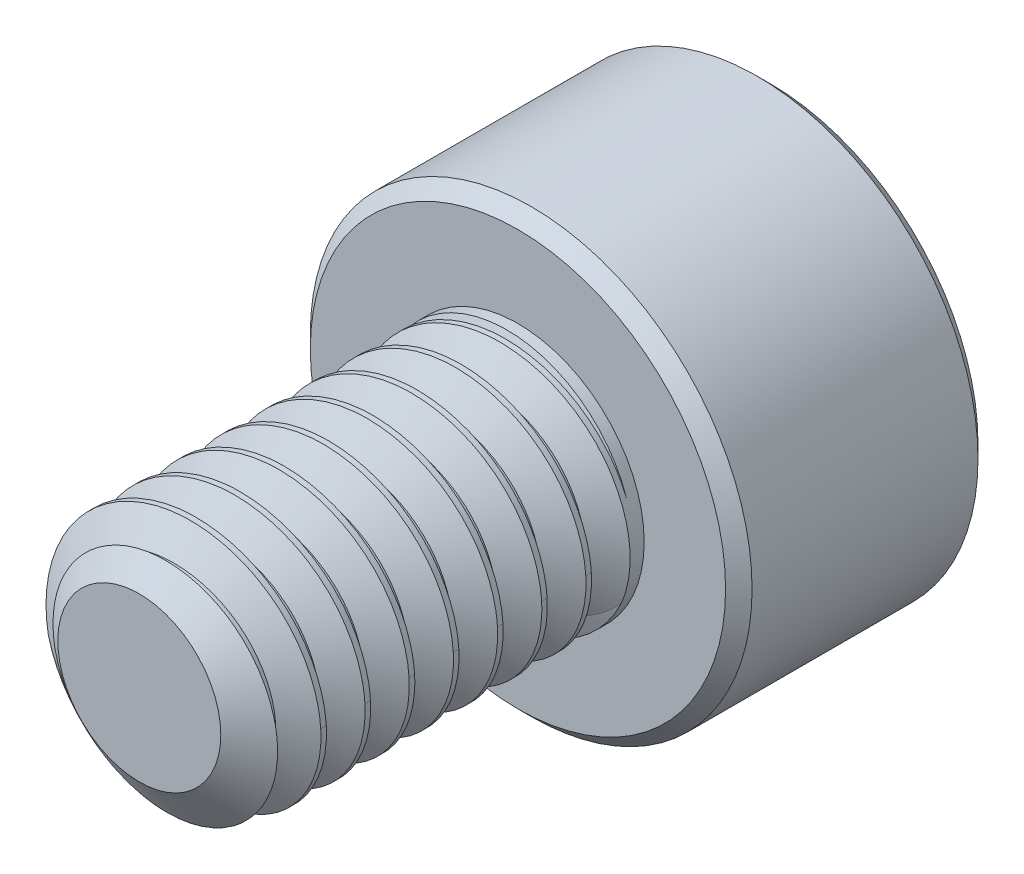
SolidWorks part; units mm, degrees
material "Plain Carbon Steel"
ref_plane "Front Plane" through (0, 0, 0) normal (0, 0, 1) x (1, 0, 0)
ref_plane "Top Plane" through (0, 0, 0) normal (0, 1, 0) x (1, 0, 0)
ref_plane "Right Plane" through (0, 0, 0) normal (1, 0, 0) x (0, 0, -1)
sketch "Sketch1" plane through (0, 0, 0) normal (0, 0, 1) x (1, 0, 0)
  circle A0 centre (0, 0) radius 2
  dimension "OD" = 4
extrude "Extrude1" add sketch "Sketch1" against normal blind 6
sketch "Sketch2" plane through (0, 0, 0) normal (0, 0, 1) x (1, 0, 0)
  circle A0 centre (0, 0) radius 2 construction
  circle A1 centre (0, 0) radius 2
curve "Helix/Spiral1" pitch 0.7 height 6.7 radius 2 centre (0, 0, 0) axis (0, 0, -1) start towards (0, 1, 0) parameters "pitch"=0.7
sketch "Sketch3" plane through (0, 0, 0) normal (1, 0, 0) x (0, 0, -1)
  line L0 (-0.6125, 2) -> (-0.35, 1.5453)
  line L1 (-0.35, 1.5453) -> (-0.2625, 1.5453)
  line L2 (-0.2625, 1.5453) -> (0, 2)
  line L3 (-0.6125, 2) -> (0, 2)
  line L4 (-0.3063, 2) -> (-0.3063, 1.5453) construction
  line L5 (-0.4813, 1.7727) -> (-0.1313, 1.7727) construction
  line L6 (0, 2) -> (0, -2) construction
  line L7 (0, -2) -> (6, -2) construction
  point P11 (3.15, -2)
  dimension "D1" = 0.0875
  dimension "D2" = 0.35
  dimension "D3" = 60
  dimension "D4" = 3.15
sweep "Cut-Sweep1" cut profiles "Sketch3" path "Helix/Spiral1" align with end faces yes
sketch "Sketch4" plane through (0, 0, 0) normal (1, 0, 0) x (0, 0, -1)
  line L0 (0.4962, 2) -> (0, 1.2913)
  line L1 (0, 1.2913) -> (0, 2)
  line L2 (0.4962, 2) -> (0, 2)
  line L3 (-0.6125, 2) -> (0, 2) construction
  line L4 (0, 0) -> (7.0209, 0) construction
  dimension "D1" = 55
  dimension "D2" = 0.254
revolve "Cut-Revolve1" cut sketch "Sketch4" angle 360 about L4
sketch "Sketch5" plane through (0, 0, 0) normal (1, 0, 0) x (0, 0, -1)
  line L0 (6, -1.8828) -> (6, 1.3901) construction
  line L1 (6, 2) -> (0.1203, 2)
  line L2 (6, 2) -> (6, 0)
  line L3 (6, 0) -> (0.0001, 0)
  line L4 (0.0001, 1.6698) -> (0.0001, 0)
  line L5 (0.1203, 2) -> (0.0001, 1.6698)
  line L6 (0, 0) -> (9.9695, 0) construction
  point P3 (0.0001, 2)
  point P10 (0.0001, 2)
  dimension "D1" = 0.3302
  dimension "Thread min" = 0.0001
  dimension "D3" = 20
revolve "partially thread" [suppressed] add sketch "Sketch5" angle 360 about L6
sketch "Sketch6" plane through (0, 0, -6) normal (0, 0, -1) x (-1, 0, 0)
  circle A0 centre (0, 0) radius 3.5
  dimension "head dia" = 7
extrude "Extrude2" add sketch "Sketch6" along normal blind 4
sketch "Sketch7" plane through (0, 0, -10) normal (0, 0, -1) x (-1, 0, 0)
  line L1 (0, 1.7321) -> (-1.5, 0.866)
  line L2 (-1.5, 0.866) -> (-1.5, -0.866)
  line L3 (-1.5, -0.866) -> (0, -1.7321)
  line L4 (0, -1.7321) -> (1.5, -0.866)
  line L5 (1.5, -0.866) -> (1.5, 0.866)
  line L6 (1.5, 0.866) -> (0, 1.7321)
  circle A0 centre (0, 0) radius 1.5 construction
  dimension "hex dia" = 3
extrude "Cut-Extrude1" cut sketch "Sketch7" against normal blind 2.25
sketch "Sketch8" plane through (0, 0, -10) normal (0, 0, -1) x (-1, 0, 0)
  circle A0 centre (0, 0) radius 1.7321
extrude "Cut-Extrude2" cut sketch "Sketch8" against normal through all draft 45
chamfer "Chamfer1" distance 0.21 angle 45 2 edges at (-3.5, 0, -10) (-3.5, 0, -6)
sketch "Sketch9" plane through (0, 0, 0) normal (1, 0, 0) x (0, 0, -1)
  line L0 (0, 2) -> (0, -2) construction
  line L1 (3.85, 2) -> (3.85, -2) construction
  dimension "D1" = 3.85
sketch "Sketch10" plane through (0, 0, 0) normal (1, 0, 0) x (0, 0, -1)
  line L0 (6, 2) -> (6, 0)
  line L1 (6, 2) -> (5.825, 2)
  line L2 (5.825, 2) -> (4.9966, 0)
  line L3 (6, 0) -> (4.9966, 0)
  line L4 (6, 3.29) -> (6, -3.29) construction
  dimension "D1" = 22.5
  dimension "D2" = 0.175
revolve "Revolve1" add sketch "Sketch10" angle 360 about L3
equation "\"D3@Helix/Spiral1\" = \"screw length@Extrude1\"+\"pitch@Helix/Spiral1\""
equation "\"D1@Sketch3\" = \"pitch@Helix/Spiral1\"*.125"
equation "\"D2@Sketch3\" = \"pitch@Helix/Spiral1\"*.5"
equation "\"D1@Cut-Extrude1\" = \"hex dia@Sketch7\"*.75"
equation "\"D1@Chamfer1\" = \"head dia@Sketch6\"*.03"
equation "\"D1@Sketch9\" = \"pitch@Helix/Spiral1\"*5.5"
equation "\"D2@Sketch10\" = \"pitch@Helix/Spiral1\"*.25"
equation "\"D4@Sketch3\" = \"pitch@Helix/Spiral1\"*4.50"
